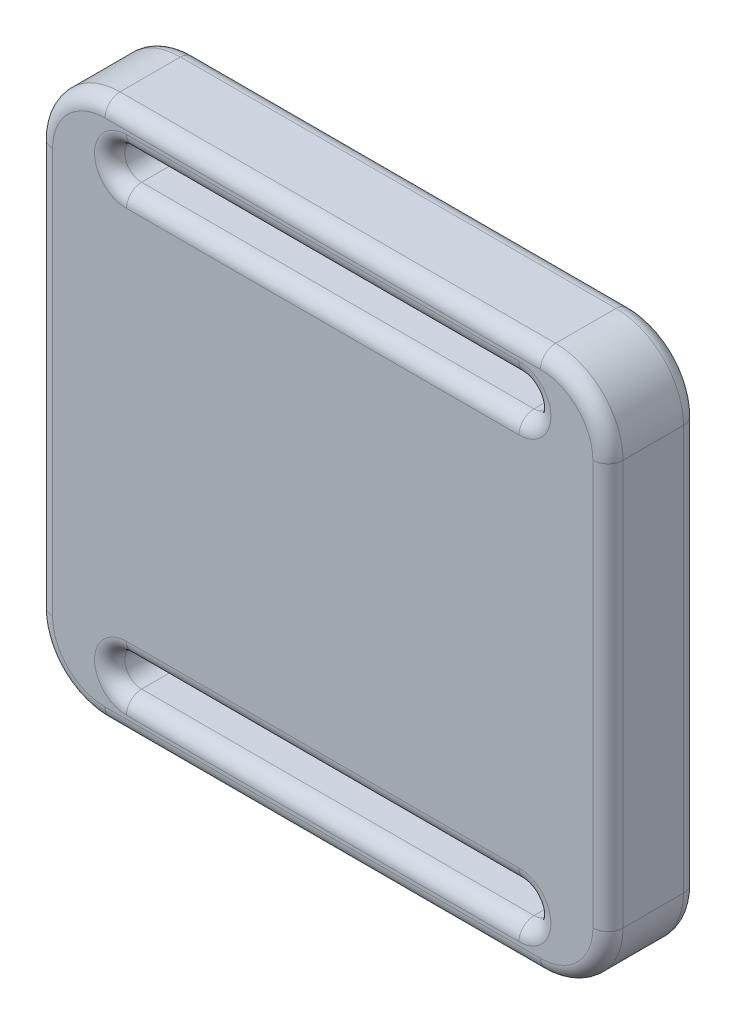
SolidWorks part; units mm, degrees
material "ABS"
ref_plane "Front Plane" through (0, 0, 0) normal (0, 0, 1) x (1, 0, 0)
ref_plane "Top Plane" through (0, 0, 0) normal (0, 1, 0) x (1, 0, 0)
ref_plane "Right Plane" through (0, 0, 0) normal (1, 0, 0) x (0, 0, -1)
ref_plane "Plane1" through (0, 0, 0.6) normal (0, 0, -1) x (-1, 0, 0)
sketch "Sketch1" plane through (0, 0, 0.6) normal (0, 0, -1) x (-1, 0, 0)
  line L0 (-4.4734, 35.787) -> (-33.3266, 35.787)
  line L1 (-37.8, 31.3136) -> (-37.8, 4.4734)
  line L2 (-33.3266, 0) -> (-4.4734, 0)
  line L3 (0, 4.4734) -> (0, 31.3136)
  line L4 (-5.9, 4.4734) -> (-31.9, 4.4734)
  line L5 (-18.9, 0) -> (-18.9, 2.2367) construction
  line L6 (-18.9, 2.2367) -> (-18.9, 4.4734) construction
  line L7 (-18.9, 35.787) -> (-18.9, 28.2965) construction
  line L13 (-5.9, 2.2367) -> (-31.9, 2.2367)
  line L16 (-5.9, 31.3139) -> (-31.9, 31.3139)
  line L17 (-31.9, 33.5505) -> (-5.9, 33.5505)
  arc A0 (0, 31.3136) -> (-4.4734, 35.787) centre (-4.4734, 31.3136) ccw
  arc A1 (-33.3266, 35.787) -> (-37.8, 31.3136) centre (-33.3266, 31.3136) ccw
  arc A2 (-37.8, 4.4734) -> (-33.3266, 0) centre (-33.3266, 4.4734) ccw
  arc A3 (-4.4734, 0) -> (0, 4.4734) centre (-4.4734, 4.4734) ccw
  arc A21 (-5.9, 4.4734) -> (-5.9, 2.2367) centre (-5.9, 3.355) cw
  arc A22 (-31.9, 2.2367) -> (-31.9, 4.4734) centre (-31.9, 3.355) cw
  arc A24 (-5.9, 33.5505) -> (-5.9, 31.3139) centre (-5.9, 32.4322) cw
  arc A25 (-31.9, 31.3139) -> (-31.9, 33.5505) centre (-31.9, 32.4322) cw
  point P12 (-18.9, 33.5505)
  dimension "D1" = 37.8
  dimension "D2" = 2.2367
  dimension "D3" = 26
  dimension "D4" = 2.2367
  dimension "D5" = 26
extrude "Boss-Extrude1" add sketch "Sketch1" against normal blind 6
sketch "Sketch2" plane through (0, 0, 0.6) normal (0, 0, -1) x (-1, 0, 0)
  line L0 (-37.8, 17.8935) -> (0, 17.8935) construction
  line L1 (-35.9, 7.3935) -> (-1.9, 7.3935)
  line L2 (-35.9, 7.3935) -> (-35.9, 28.3935)
  line L3 (-35.9, 28.3935) -> (-1.9, 28.3935)
  line L4 (-1.9, 7.3935) -> (-1.9, 28.3935)
  line L5 (-35.9, 7.3935) -> (-1.9, 28.3935) construction
  line L6 (-35.9, 28.3935) -> (-1.9, 7.3935) construction
  line L7 (-37.8, 31.3136) -> (-37.8, 4.4734) construction
  line L8 (0, 4.4734) -> (0, 31.3136) construction
  point P0 (-18.9, 17.8935)
extrude "Cut-Extrude1" cut sketch "Sketch2" against normal blind 5.5
fillet "Fillet1" radius 1 32 edges at (18.9, 35.787, 6.6) (36.4898, 34.4768, 6.6) (37.8, 17.8935, 6.6) (36.4898, 1.3102, 6.6) (18.9, 0, 6.6) (1.3102, 1.3102, 6.6) (0, 17.8935, 6.6) (1.3102, 34.4768, 6.6) (33.0183, 3.355, 6.6) (18.9, 4.4734, 6.6) (4.7817, 3.355, 6.6) (18.9, 2.2367, 6.6) (33.0183, 32.4322, 6.6) (18.9, 33.5505, 6.6) (4.7817, 32.4322, 6.6) (18.9, 31.3139, 6.6) (0, 17.8935, 0.6) (1.3102, 1.3102, 0.6) (18.9, 0, 0.6) (36.4898, 1.3102, 0.6) (37.8, 17.8935, 0.6) (36.4898, 34.4768, 0.6) (18.9, 35.787, 0.6) (1.3102, 34.4768, 0.6) (18.9, 4.4734, 0.6) (33.0183, 3.355, 0.6) (18.9, 2.2367, 0.6) (4.7817, 3.355, 0.6) (18.9, 33.5505, 0.6) (33.0183, 32.4322, 0.6) (18.9, 31.3139, 0.6) (4.7817, 32.4322, 0.6)
sketch "Sketch3" plane through (0, 0, 0.6) normal (0, 0, -1) x (-1, 0, 0)
  line L0 (-1.9, 28.3935) -> (-4.7817, 32.4322)
  line L1 (-4.7817, 32.4322) -> (-5.9, 31.3139)
  line L2 (-5.9, 31.3139) -> (-3.8163, 28.3935)
  line L4 (-3.8163, 28.3935) -> (-1.9, 28.3935)
  point P2 (0, 0)
  point P6 (0, 0)
  point P10 (0, 0)
  point P12 (0, 0)
extrude "Cut-Extrude2" cut sketch "Sketch3" against normal blind 1
fillet "Fillet2" radius 0.5 2 edges at (2.8581, 28.3935, 1.6) (5.1092, 31.6414, 1.6)
